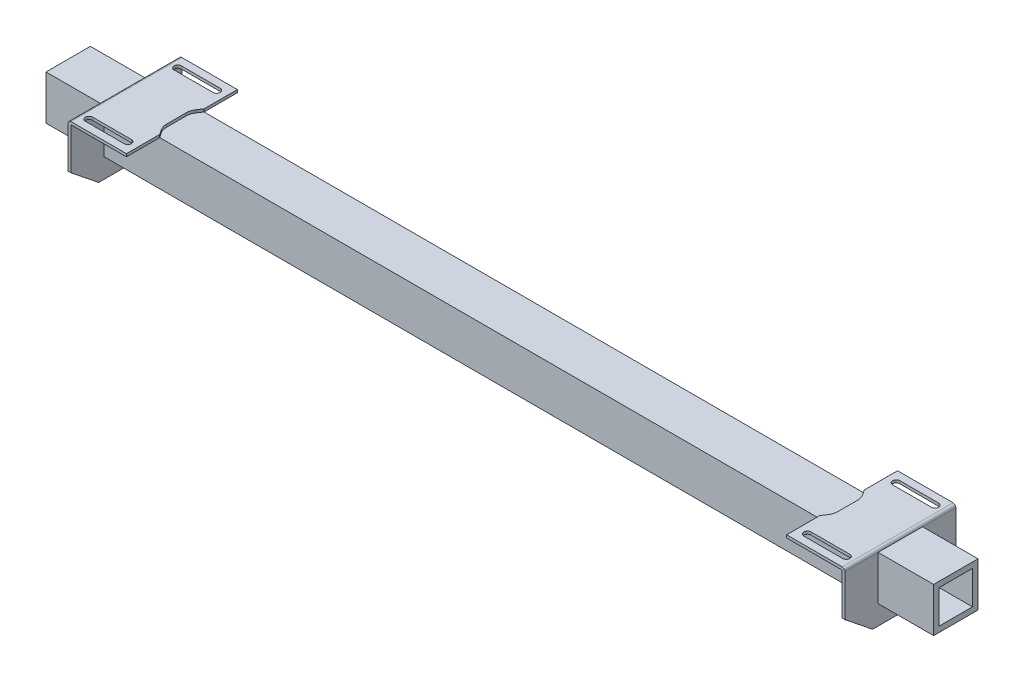
SolidWorks part; units mm, degrees
ref_plane "Front Plane" through (0, 0, 0) normal (0, 0, 1) x (1, 0, 0)
ref_plane "Top Plane" through (0, 0, 0) normal (0, 1, 0) x (1, 0, 0)
ref_plane "Right Plane" through (0, 0, 0) normal (1, 0, 0) x (0, 0, -1)
sketch "Sketch3" plane through (0, 0, 0) normal (1, 0, 0) x (0, 0, -1)
  line L1 (0, 0) -> (80, 0)
  line L2 (0, 0) -> (0, 80)
  line L3 (0, 80) -> (80, 80)
  line L4 (80, 0) -> (80, 80)
  line L5 (10, 70) -> (70, 70)
  line L6 (10, 70) -> (10, 10)
  line L7 (10, 10) -> (70, 10)
  line L8 (70, 70) -> (70, 10)
  dimension "D1" = 80
  dimension "D2" = 80
  dimension "D3" = 10
  dimension "D4" = 10
  dimension "D5" = 10
  dimension "D6" = 10
extrude "Boss-Extrude2" add sketch "Sketch3" along normal blind 1600
ref_plane "Plane1" through (1495, 0, 0) normal (1, 0, 0) x (0, 0, -1)
sketch "Sketch7" plane through (1495, 0, 0) normal (1, 0, 0) x (0, 0, -1)
  line L0 (-60, 85) -> (140, 85)
  line L1 (140, 85) -> (140, 5)
  line L2 (140, 5) -> (90, -35)
  line L3 (90, -35) -> (-10, -35)
  line L4 (-10, -35) -> (-60, 5)
  line L5 (-60, 5) -> (-60, 85)
  line L6 (80, 80) -> (0, 80) construction
  line L7 (70, 70) -> (10, 70) construction
  line L8 (70, 70) -> (10, 70)
  line L9 (70, 10) -> (70, 70) construction
  line L10 (10, 10) -> (70, 10) construction
  line L11 (10, 70) -> (10, 10) construction
  line L12 (70, 10) -> (70, 70)
  line L13 (10, 10) -> (70, 10)
  line L14 (10, 70) -> (10, 10)
  point P10 (40, 85)
  point P11 (40, 80)
  dimension "D1" = 200
  dimension "D2" = 120
  dimension "D3" = 50
  dimension "D4" = 50
  dimension "D5" = 5
  dimension "D6" = 40
extrude "Boss-Extrude3" add sketch "Sketch7" along normal blind 5
sketch "Sketch8" plane through (0, 0, -80) normal (0, 0, -1) x (-1, 0, 0)
  line L0 (-1500, 85) -> (-1495, 85) construction
  line L1 (-1500, 85) -> (-1395, 85)
  line L2 (-1500, 85) -> (-1500, 80)
  line L3 (-1500, 80) -> (-1395, 80)
  line L4 (-1395, 85) -> (-1395, 80)
  line L5 (-1500, 5) -> (-1500, 85) construction
  dimension "D1" = 5
  dimension "D2" = 105
extrude "Boss-Extrude4" add sketch "Sketch8" along normal up to surface and the other way up to surface up to face at (1497.5, 45, -140) other way up to face at (1497.5, 45, 60)
sketch "Sketch9" plane through (0, 85, 0) normal (0, 1, 0) x (1, 0, 0)
  line L0 (1395, 80) -> (1400.8013, 71.2981)
  line L1 (1395, 140) -> (1395, -60) construction
  line L2 (1405, 57.4306) -> (1405, 22.5694)
  line L3 (1400.8013, 8.7019) -> (1395, 0)
  line L4 (1395, 0) -> (0, 0) construction
  line L5 (1395, 0) -> (1395, 80)
  line L6 (1600, 80) -> (1600, 0) construction
  arc A0 (1405, 22.5694) -> (1400.8013, 8.7019) centre (1380, 22.5694) cw
  arc A1 (1400.8013, 71.2981) -> (1405, 57.4306) centre (1380, 57.4306) cw
  point P15 (1405, 15)
  point P18 (1405, 65)
  dimension "D4" = 25
  dimension "D1" = 10
  dimension "D2" = 15
  dimension "D3" = 15
extrude "Cut-Extrude1" cut sketch "Sketch9" against normal up to surface (5 mm away) up to face at (1445, 80, 30)
sketch "Sketch10" plane through (0, 85, 0) normal (0, 1, 0) x (1, 0, 0)
  line L0 (1412.5, 120) -> (1482.5, 120) construction
  line L1 (1412.5, 126.5) -> (1482.5, 126.5)
  line L2 (1412.5, 113.5) -> (1482.5, 113.5)
  line L3 (1412.5, -40) -> (1482.5, -40) construction
  line L4 (1412.5, -33.5) -> (1482.5, -33.5)
  line L5 (1412.5, -46.5) -> (1482.5, -46.5)
  line L6 (1500, 140) -> (1395, 140) construction
  arc A0 (1412.5, 126.5) -> (1412.5, 113.5) centre (1412.5, 120) ccw
  arc A1 (1482.5, 113.5) -> (1482.5, 126.5) centre (1482.5, 120) ccw
  arc A2 (1412.5, -33.5) -> (1412.5, -46.5) centre (1412.5, -40) ccw
  arc A3 (1482.5, -46.5) -> (1482.5, -33.5) centre (1482.5, -40) ccw
  point P2 (1447.5, 120)
  point P7 (1447.5, -40)
  point P16 (1447.5, 140)
  point P17 (1447.5, 126.5)
  dimension "D1" = 70
  dimension "D2" = 13
  dimension "D3" = 13
  dimension "D4" = 160
  dimension "D5" = 20
extrude "Cut-Extrude2" cut sketch "Sketch10" against normal up to next
fillet "Fillet1" radius 5 1 edges at (1500, 85, -40)
ref_plane "Plane2" through (800, 0, 0) normal (1, 0, 0) x (0, 0, -1)
mirror "Mirror1" about plane through (800, 0, 0) normal (1, 0, 0) of "Fillet1", "Boss-Extrude3"
mirror "Mirror2" about plane through (800, 0, 0) normal (1, 0, 0) of "Fillet1", "Cut-Extrude2", "Boss-Extrude3", "Boss-Extrude4", "Cut-Extrude1"
sketch "Sketch13" plane through (0, 0, 0) normal (0, 0, 1) x (1, 0, 0)
  line L0 (0, 40) -> (2446.8223, 40) construction
  line L1 (0, 80) -> (0, 0) construction
sketch "Sketch14" plane through (0, 80, 0) normal (0, 1, 0) x (1, 0, 0)
  line L0 (800, 80) -> (800, 0) construction
  line L1 (1495, 80) -> (105, 80) construction
  line L2 (1495, 0) -> (105, 0) construction
  line L3 (706.4267, 40) -> (893.5733, 40) construction
  point P8 (800, 40)
equation "\"D2@Sketch3\"=\"D1@Sketch3\""
equation "\"D4@Sketch3\"=\"D3@Sketch3\""
equation "\"D5@Sketch3\"=\"D3@Sketch3\""
equation "\"D6@Sketch3\"=\"D3@Sketch3\""
equation "\"D3@Sketch9\"=\"D2@Sketch9\""
